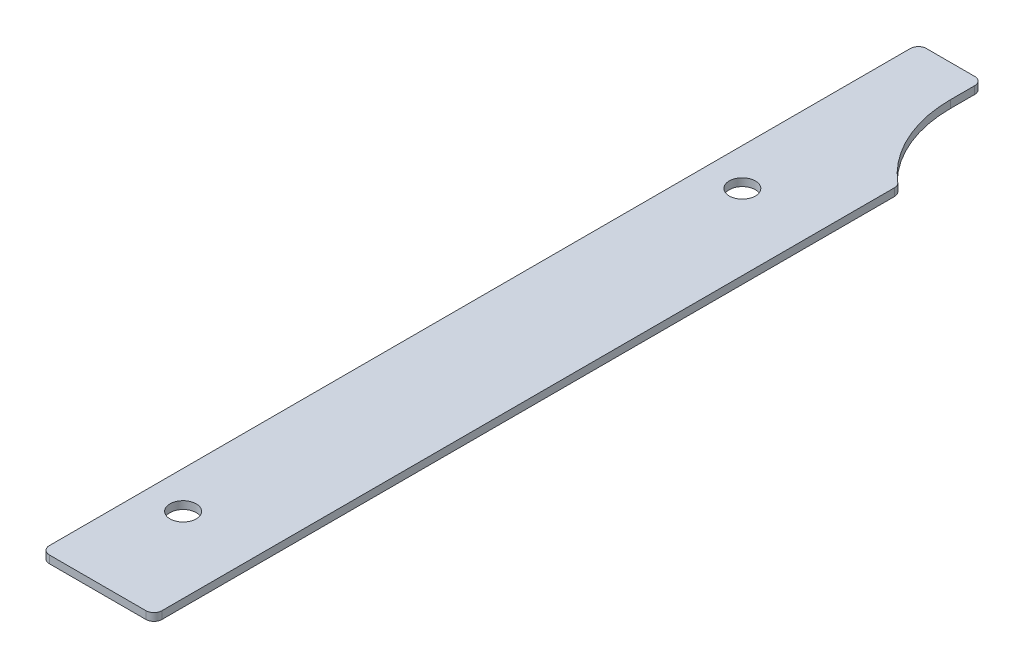
SolidWorks part; units mm, degrees
material "Plain Carbon Steel"
ref_plane "Front" through (0, 0, 0) normal (0, 0, 1) x (1, 0, 0)
ref_plane "Top" through (0, 0, 0) normal (0, 1, 0) x (1, 0, 0)
ref_plane "Right" through (0, 0, 0) normal (1, 0, 0) x (0, 0, -1)
sketch "Sketch1" plane through (0, 0, 0) normal (0, 1, 0) x (1, 0, 0)
  line L1 (22.225, -173.0375) -> (-22.225, -173.0375)
  line L2 (22.225, -173.0375) -> (22.225, 173.0375)
  line L3 (22.225, 173.0375) -> (-22.225, 173.0375)
  line L4 (-22.225, -173.0375) -> (-22.225, 173.0375)
  line L5 (22.225, -173.0375) -> (-22.225, 173.0375) construction
  line L6 (22.225, 173.0375) -> (-22.225, -173.0375) construction
  point P0 (0, 0)
  dimension "D1" = 346.075
  dimension "D2" = 44.45
base flange "Base-Flange1" sketch "Sketch1" thickness 3.0226 reverse thickness direction no parameters "D1"=3.7592
sketch "Sketch6" plane through (0, 0, 0) normal (0, 1, 0) x (1, 0, 0)
  line L0 (-22.225, -173.0375) -> (22.225, -173.0375) construction
  line L1 (22.225, -173.0375) -> (22.225, 173.0375) construction
  line L3 (22.225, 173.0375) -> (3.175, 173.0375)
  line L4 (22.225, 173.0375) -> (22.225, 120.65)
  line L5 (22.225, 120.65) -> (3.175, 120.65)
  line L6 (3.175, 173.0375) -> (3.175, 120.65)
  circle A2 centre (-7.5406, -131.7625) radius 5.1594
  circle A3 centre (-7.5406, 88.9) radius 5.1594
  dimension "D1" = 261.9375
  dimension "D3" = 10.3188
  dimension "D2" = 41.275
  dimension "D5" = 29.7656
  dimension "D6" = 52.3875
  dimension "D7" = 19.05
extrude "Cut-Extrude1" cut sketch "Sketch6" against normal up to next normal cut yes
fillet "Fillet2" radius 50.8 1 edges at (3.175, -1.5113, -120.65)
fillet "Fillet3" radius 3.175 5 edges at (3.175, -1.5113, -173.0375) (-22.225, -1.5113, -173.0375) (22.225, -1.5113, -120.65) (-22.225, -1.5113, 173.0375) (22.225, -1.5113, 173.0375)
sketch "Bend-Lines1" [suppressed] plane through (0, 0, 0) normal (0, 1, 0) x (1, 0, 0)
sketch "Bounding-Box1" [suppressed] plane through (0, 0, 0) normal (0, 1, 0) x (1, 0, 0)
sheet metal parameters "Sheet-Metal28" thickness 3.0226 parameters "D1"=3.7592
flat pattern "Flat-Pattern28" [suppressed]
sketch "Bend-Lines2" plane through (0, 0, 0) normal (0, 1, 0) x (1, 0, 0)
sketch3d "Bounding-Box2" [suppressed]
  line L0 (38.1, 173.0375, 0) -> (38.1, -173.0375, 0) construction
  line L1 (-38.1, 173.0375, 0) -> (-38.1, -173.0375, 0) construction
  line L2 (38.1, 173.0375, 0) -> (-38.1, 173.0375, 0) construction
  line L3 (38.1, -173.0375, 0) -> (-38.1, -173.0375, 0) construction
sheet metal parameters "Sheet-Metal29" thickness 3.0226 parameters "D1"=3.7592
flat pattern "Flat-Pattern28"
sketch "Bend-Lines2" plane through (0, 0, 0) normal (0, 1, 0) x (1, 0, 0)
sketch3d "Bounding-Box2" [suppressed]
  line L0 (22.2254, 173.0374, 0) -> (22.225, -173.0375, 0) construction
  line L1 (-22.2246, 173.0375, 0) -> (-22.225, -173.0374, 0) construction
  line L2 (22.2254, 173.0374, 0) -> (-22.2246, 173.0375, 0) construction
  line L3 (22.225, -173.0375, 0) -> (-22.225, -173.0374, 0) construction
equation "\"Total Cutting Length\"= \"Cutting Length-Outer\" + \"Cutting Length-Inner\""
equation "\"Amount in ft^2\"= \"Bounding Box Area-Blank\" / 144"
